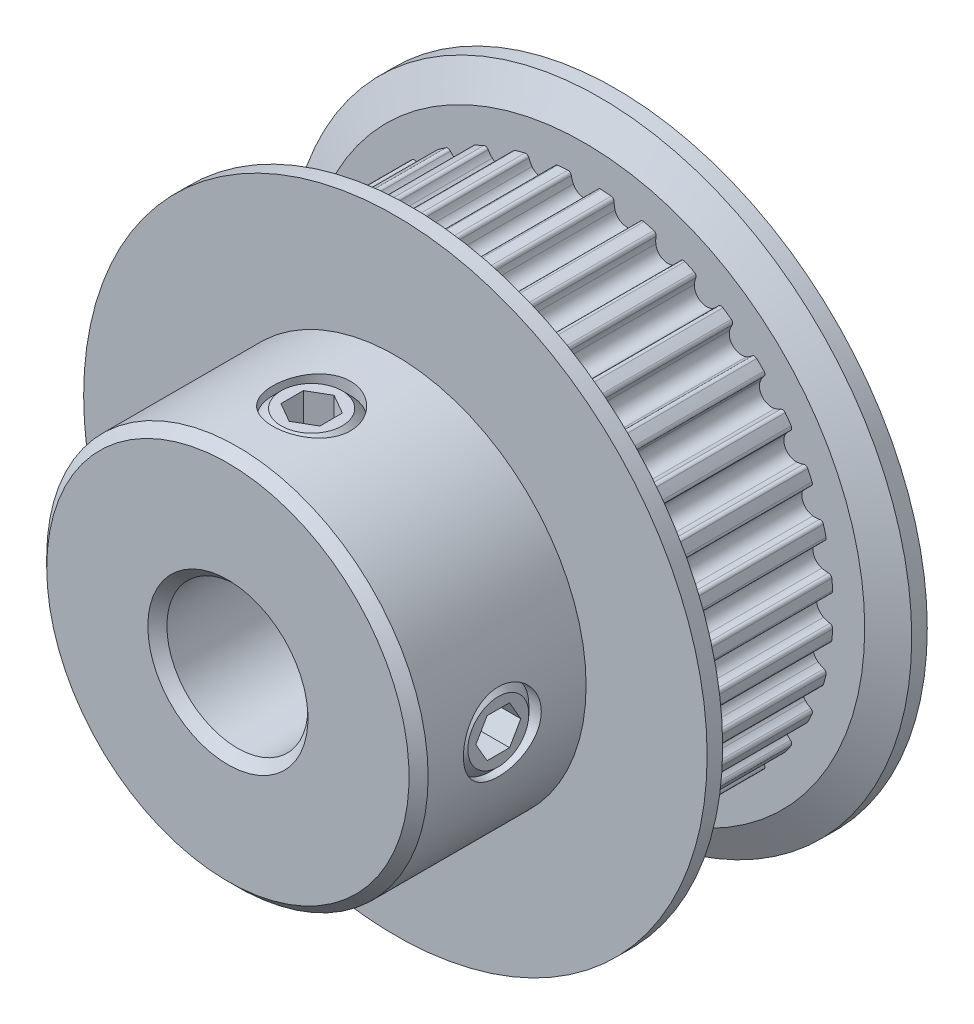
SolidWorks part; units mm, degrees
ref_plane "Front Plane" through (0, 0, 0) normal (0, 0, 1) x (1, 0, 0)
ref_plane "Top Plane" through (0, 0, 0) normal (0, 1, 0) x (1, 0, 0)
ref_plane "Right Plane" through (0, 0, 0) normal (1, 0, 0) x (0, 0, -1)
sketch "Sketch1" plane through (0, 0, 0) normal (0, 0, 1) x (1, 0, 0)
  line L1 (-1.8459, 10.4515) -> (1.8459, 10.4515) construction
  line L4 (0, 0) -> (0, 10.4515) construction
  line L5 (0, 10.4515) -> (0, 14.0238) construction
  line L6 (0, 11.4555) -> (1.9924, 11.2809) construction
  line L7 (1.9924, 11.2809) -> (2.8218, 11.1344) construction
  line L8 (1.9924, 11.2809) -> (1.8459, 10.4515) construction
  line L9 (-1.9924, 11.2809) -> (-1.8459, 10.4515) construction
  line L10 (-1.9482, 11.0308) -> (-2.4785, 14.0335)
  line L11 (-2.4785, 14.0335) -> (2.4785, 14.0335)
  line L12 (2.4785, 14.0335) -> (1.9482, 11.0308)
  circle A0 centre (0, 0) radius 11.4555 construction
  circle A1 centre (0, 0) radius 14.0335 construction
  circle A2 centre (0, 0) radius 11.2015 construction
  arc A3 (-0.4989, 10.7633) -> (0.4989, 10.7633) centre (0, 11.0065) ccw
  arc A4 (-0.4989, 10.7633) -> (-0.5884, 11.0497) centre (0.4, 11.2015) cw
  arc A5 (-1.9482, 11.0308) -> (-0.7467, 11.1766) centre (0, 0) cw
  arc A6 (-0.5884, 11.0497) -> (-0.7467, 11.1766) centre (-0.7367, 11.0269) ccw
  arc A7 (1.9482, 11.0308) -> (0.7467, 11.1766) centre (0, 0) ccw
  arc A8 (0.5884, 11.0497) -> (0.7467, 11.1766) centre (0.7367, 11.0269) cw
  arc A9 (0.4989, 10.7633) -> (0.5884, 11.0497) centre (-0.4, 11.2015) ccw
  point P6 (0, 20.9083)
  point P11 (0, 11.4555)
  point P13 (0, 14.0335)
  point P14 (0, 11.2015)
  dimension "D1" = 6.8846
  dimension "D2" = 2.5683
sketch "Sketch2" plane through (0, 0, 0) normal (1, 0, 0) x (0, 0, -1)
  line L0 (-8.7249, 3.175) -> (8.7249, 3.175)
  line L1 (-8.7249, 3.175) -> (-8.7249, 8.585)
  line L2 (-8.7249, 8.585) -> (-1.1851, 8.585)
  line L3 (-1.1851, 8.585) -> (-1.1851, 14.0335)
  line L4 (-1.1851, 14.0335) -> (0.2149, 14.0335) construction
  line L5 (0.2149, 14.0335) -> (0.2149, 11.2015) construction
  line L6 (0.2149, 11.2015) -> (7.3249, 11.2015)
  line L7 (7.3249, 11.2015) -> (7.3249, 14.0335) construction
  line L8 (7.3249, 14.0335) -> (8.7249, 14.0335) construction
  line L9 (8.7249, 14.0335) -> (8.7249, 3.175)
  line L10 (-8.7249, 0) -> (8.7249, 0) construction
  line L11 (8.0249, 14.0335) -> (7.3249, 12.6175)
  line L12 (0.2149, 12.6175) -> (-0.4851, 14.0335)
  line L13 (-1.1851, 14.0335) -> (-0.4851, 14.0335)
  line L14 (0.2149, 12.6175) -> (0.2149, 11.2015)
  line L15 (7.3249, 11.2015) -> (7.3249, 12.6175)
  line L16 (8.0249, 14.0335) -> (8.7249, 14.0335)
  arc A0 (0.2149, 12.6175) -> (-0.4851, 14.0335) centre (-1.5673, 12.6175) ccw construction
  arc A1 (7.3249, 12.6175) -> (8.0249, 14.0335) centre (9.1071, 12.6175) cw construction
  point P12 (0.2149, 12.6175)
  point P14 (-0.4851, 14.0335)
  point P20 (7.3249, 12.6175)
  point P21 (8.0249, 14.0335)
  point P25 (7.3249, 0)
  point P26 (0.2149, 0)
revolve "Revolve1" add sketch "Sketch2" angle 360 mid plane about L10
sketch "Sketch3" plane through (0, 0, 0) normal (0, 0, 1) x (1, 0, 0)
  line L6 (2.4785, 14.0335) -> (-2.4785, 14.0335)
  line L7 (1.9482, 11.0308) -> (2.4785, 14.0335)
  line L8 (-2.4785, 14.0335) -> (-1.9482, 11.0308)
  line L9 (2.4785, 14.0335) -> (-2.4785, 14.0335)
  line L10 (1.9482, 11.0308) -> (2.4785, 14.0335)
  line L11 (-2.4785, 14.0335) -> (-1.9482, 11.0308)
  arc A8 (1.9482, 11.0308) -> (0.7467, 11.1766) centre (0, 0) ccw
  arc A9 (0.7467, 11.1766) -> (0.5884, 11.0497) centre (0.7367, 11.0269) ccw
  arc A10 (0.4989, 10.7633) -> (0.5884, 11.0497) centre (-0.4, 11.2015) ccw
  arc A11 (-0.4989, 10.7633) -> (0.4989, 10.7633) centre (0, 11.0065) ccw
  arc A12 (-0.5884, 11.0497) -> (-0.4989, 10.7633) centre (0.4, 11.2015) ccw
  arc A13 (-0.5884, 11.0497) -> (-0.7467, 11.1766) centre (-0.7367, 11.0269) ccw
  arc A14 (-0.7467, 11.1766) -> (-1.9482, 11.0308) centre (0, 0) ccw
  arc A15 (1.9482, 11.0308) -> (0.7467, 11.1766) centre (0, 0) ccw
  arc A16 (0.7467, 11.1766) -> (0.5884, 11.0497) centre (0.7367, 11.0269) ccw
  arc A17 (0.4989, 10.7633) -> (0.5884, 11.0497) centre (-0.4, 11.2015) ccw
  arc A18 (-0.4989, 10.7633) -> (0.4989, 10.7633) centre (0, 11.0065) ccw
  arc A19 (-0.5884, 11.0497) -> (-0.4989, 10.7633) centre (0.4, 11.2015) ccw
  arc A20 (-0.5884, 11.0497) -> (-0.7467, 11.1766) centre (-0.7367, 11.0269) ccw
  arc A21 (-0.7467, 11.1766) -> (-1.9482, 11.0308) centre (0, 0) ccw
  dimension "D1" = 0
extrude "Cut-Extrude1" cut sketch "Sketch3" against normal up to vertex (7.3249 mm away) from vertex up to point (0, 11.2015, -7.3249) starting at point (0, 11.2015, -0.2149)
pattern_circular "CirPattern1" count 36 over 360 about axis through (0, 0, 8.7249) along (0, 0, 1) of "Cut-Extrude1"
sketch "Sketch4" plane through (0, 0, 0) normal (1, 0, 0) x (0, -1, 0)
  line L0 (0, -1.1851) -> (0, -8.7249) construction
  line L1 (-8.585, -1.1851) -> (8.585, -1.1851) construction
  line L2 (-8.585, -8.7249) -> (8.585, -8.7249) construction
  circle A0 centre (0, -4.955) radius 1.7526
extrude "Cut-Extrude2" cut sketch "Sketch4" along normal through all
ref_plane "Plane1" through (0, 0, 4.955) normal (0, 0, 1) x (1, 0, 0)
sketch "Sketch5" plane through (0, 0, 4.955) normal (0, 0, 1) x (1, 0, 0)
  line L0 (0, 0.1664) -> (0, 8.585) construction
  line L1 (3.175, -1.3716) -> (3.175, 0)
  line L2 (3.556, -1.7526) -> (8.0232, -1.7526)
  line L3 (3.175, 0) -> (8.585, 0) construction
  line L4 (3.175, 0) -> (8.4042, 0)
  line L5 (8.4042, 0) -> (8.4042, -1.3716)
  line L6 (3.556, -1.7526) -> (3.175, -1.3716)
  line L7 (8.4042, -1.3716) -> (8.0232, -1.7526)
  circle A0 centre (0, 0) radius 8.585 construction
  circle A1 centre (0, 0) radius 3.175 construction
  point P2 (3.175, -1.7526)
  point P11 (8.4042, -1.7526)
revolve "Revolve2" add sketch "Sketch5" angle 360 mid plane about L4
sketch "Sketch6" plane through (8.4042, 5.3841, 0) normal (-1, 0, 0) x (0, -1, 0)
  line L1 (5.3841, 5.9669) -> (4.5078, 5.4609)
  line L2 (4.5078, 5.4609) -> (4.5078, 4.4491)
  line L3 (4.5078, 4.4491) -> (5.3841, 3.9431)
  line L4 (5.3841, 3.9431) -> (6.2604, 4.4491)
  line L5 (6.2604, 4.4491) -> (6.2604, 5.4609)
  line L6 (6.2604, 5.4609) -> (5.3841, 5.9669)
  circle A0 centre (5.3841, 4.955) radius 0.8763 construction
  dimension "D1" = 1.7526
extrude "Cut-Extrude3" cut sketch "Sketch6" along normal blind 1.3144
pattern_circular "CirPattern2" count 2 over 90 about axis through (0, 0, 8.7249) along (0, 0, 1) of "Cut-Extrude2", "Revolve2", "Cut-Extrude3"
chamfer "Chamfer1" distance 0.4293 angle 45 2 edges at (3.175, 0, 8.7249) (8.585, 0, 8.7249)
ref_axis "Center Axis 1" through (0, 0, -8.7249) along (0, 0, 1)
ref_plane "Contact Plane 1" through (0, 0, 8.7249) normal (0, 0, 1) x (1, 0, 0)
ref_plane "Contact Plane 2" through (0, 0, -8.7249) normal (0, 0, -1) x (-1, 0, 0)
equation "\"D2@Sketch1\" = \"D1@Sketch1\"/2"
equation "\"D1@Sketch6\" = \"Set Screw@Sketch4\" / 2"
equation "\"D1@Cut-Extrude3\" = \"D1@Sketch6\"*.75"
equation "\"D1@Chamfer1\"=\"Hub Dia@Sketch2\"*.025"
